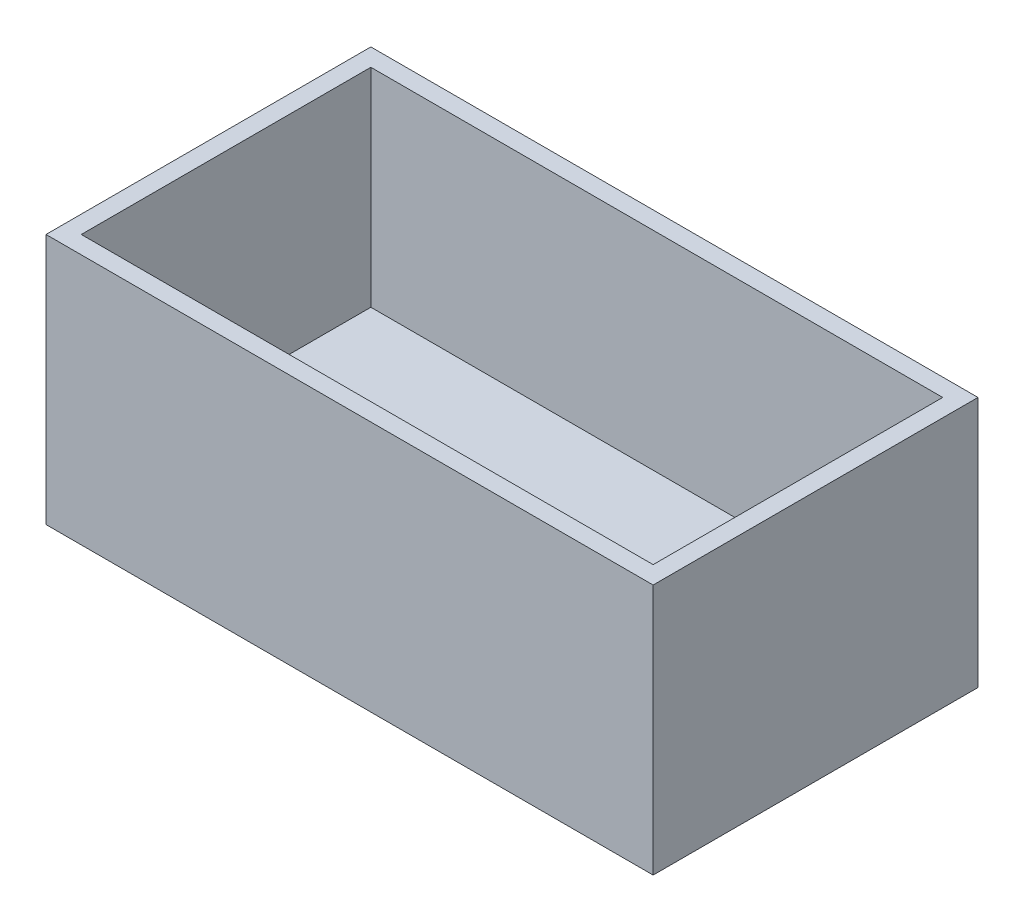
SolidWorks part; units mm, degrees
ref_plane "Front Plane" through (0, 0, 0) normal (0, 0, 1) x (1, 0, 0)
ref_plane "Top Plane" through (0, 0, 0) normal (0, 1, 0) x (1, 0, 0)
ref_plane "Right Plane" through (0, 0, 0) normal (1, 0, 0) x (0, 0, -1)
ref_axis "Axis1" through (0, 0, -88.99) along (0, 0, 1)
ref_axis "Axis2" through (0, -55, 0) along (0, 1, 0)
ref_axis "Axis3" through (-88.99, 0, 0) along (1, 0, 0)
sketch "Sketch1" plane through (0, 0, 0) normal (0, 1, 0) x (1, 0, 0)
  line L1 (617.474, -312.674) -> (-617.474, -312.674)
  line L2 (617.474, -312.674) -> (617.474, 312.674)
  line L3 (617.474, 312.674) -> (-617.474, 312.674)
  line L4 (-617.474, -312.674) -> (-617.474, 312.674)
  line L5 (617.474, -312.674) -> (-617.474, 312.674) construction
  line L6 (617.474, 312.674) -> (-617.474, -312.674) construction
  line L7 (655.574, -350.774) -> (-655.574, -350.774)
  line L8 (655.574, -350.774) -> (655.574, 350.774)
  line L9 (655.574, 350.774) -> (-655.574, 350.774)
  line L10 (-655.574, -350.774) -> (-655.574, 350.774)
  line L11 (655.574, -350.774) -> (-655.574, 350.774) construction
  line L12 (655.574, 350.774) -> (-655.574, -350.774) construction
  point P0 (0, 0)
  point P6 (0, 0)
  dimension "D1" = 1234.948
  dimension "D2" = 625.348
  dimension "D3" = 701.548
  dimension "D4" = 1311.148
extrude "Boss-Extrude1" add sketch "Sketch1" along normal blind 542.544 contours L9 L10 L7 L8
extrude "Cut-Extrude1" cut sketch "Sketch1<4>" against normal blind 448.818 from surface contours L3 L4 L1 L2 starting at face at (0, 542.544, 0)
sketch "Sketch1<4>" plane through (0, 0, 0) normal (0, 1, 0) x (1, 0, 0) same geometry as "Sketch1"
